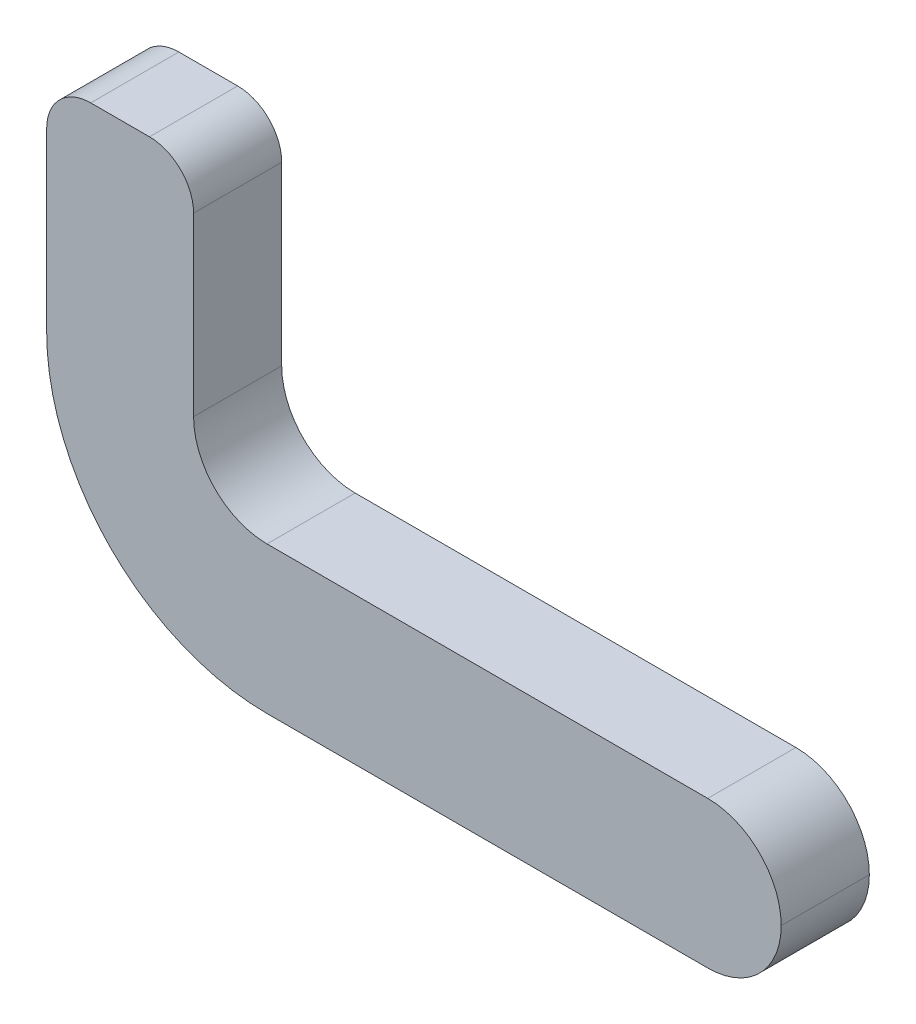
SolidWorks part; units mm, degrees
ref_plane "Front Plane" through (0, 0, 0) normal (0, 0, 1) x (1, 0, 0)
ref_plane "Top Plane" through (0, 0, 0) normal (0, 1, 0) x (1, 0, 0)
ref_plane "Right Plane" through (0, 0, 0) normal (1, 0, 0) x (0, 0, -1)
sketch "Sketch1" plane through (0, 0, 0) normal (0, 0, 1) x (1, 0, 0)
  line L0 (-16.1713, 0) -> (3.62, 0) construction
  line L1 (-14.4091, 1.8788) -> (-2.1391, 2.9204)
  line L3 (-14.4156, -1.9577) -> (-2.1391, -2.9204)
  arc A0 (-14.4091, 1.8788) -> (-14.3968, -1.9591) centre (-14.2463, -0.0397) ccw
  arc A1 (-2.1391, -2.9204) -> (-2.1391, 2.9204) centre (0, 0) ccw
  point P5 (-16.1713, 0)
  point P7 (3.62, 0)
  dimension "D3" = 5.8407
  dimension "D1" = 1.9254
  dimension "D2" = 3.62
  dimension "D4" = 12.27
  dimension "D5" = 14.2463
sketch "Sketch2" plane through (0, 0, 0) normal (0, 0, 1) x (1, 0, 0)
  line L0 (5, 0) -> (-45, 0) construction
  line L1 (-35, 5) -> (5, 5)
  line L2 (-45, 5) -> (-45, -5)
  line L3 (-45, -5) -> (5, -5)
  line L4 (5, 5) -> (5, -5)
  line L5 (-16.1713, 0) -> (3.62, 0) construction
  line L8 (-35, 5) -> (-35, 25)
  line L9 (-35, 25) -> (-45, 25)
  line L10 (-45, 5) -> (-45, 25)
  dimension "D1" = 10
  dimension "D2" = 50
  dimension "D3" = 5
  dimension "D4" = 10
  dimension "D5" = 20
extrude "Boss-Extrude1" add sketch "Sketch2" against normal blind 6 contours L2 L3 L4 L1 L8 L9 L10
fillet "Fillet1" radius 5 1 edges at (-35, 5, -3)
fillet "Fillet2" radius 15 1 edges at (-45, -5, -3)
fillet "Fillet3" radius 5 1 edges at (5, 5, -3)
fillet "Fillet4" radius 5 1 edges at (5, -5, -3)
fillet "Fillet5" radius 3 1 edges at (-35, 25, -3)
fillet "Fillet6" radius 3 1 edges at (-45, 25, -3)
